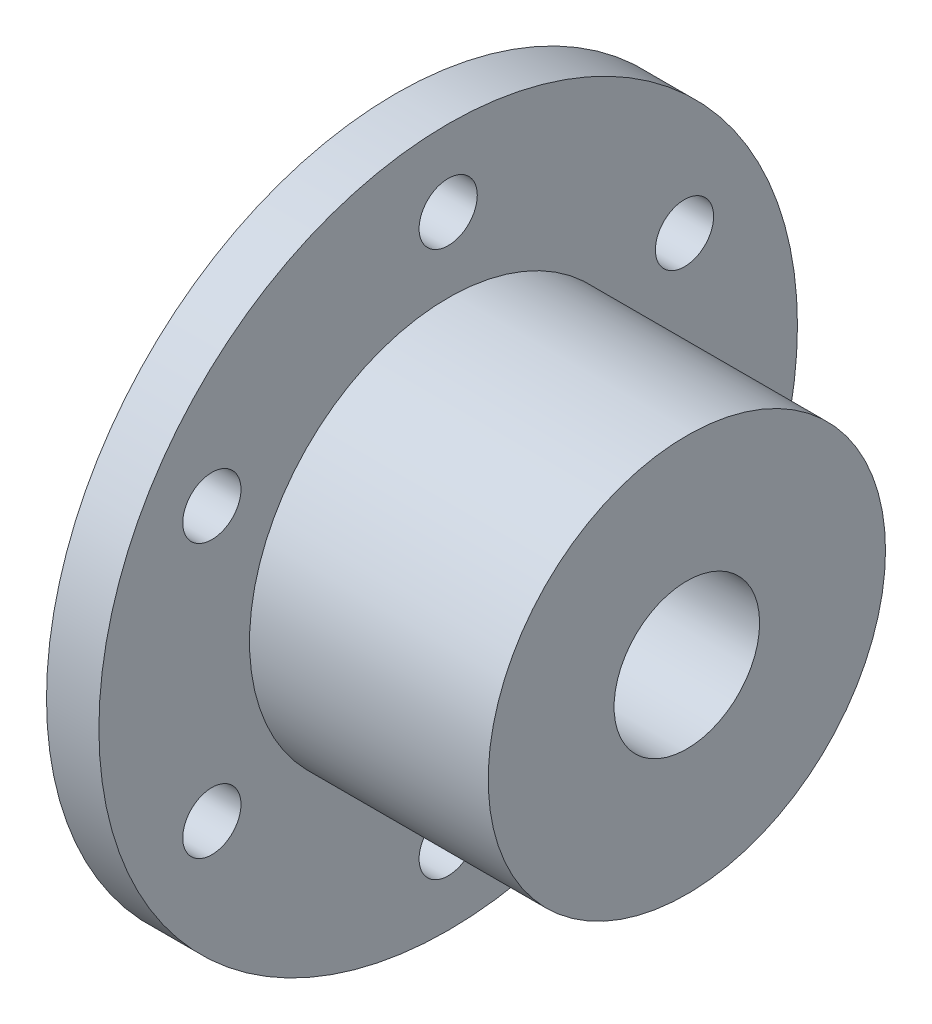
SolidWorks part; units mm, degrees
ref_plane "Front Plane" through (0, 0, 0) normal (0, 0, 1) x (1, 0, 0)
ref_plane "Top Plane" through (0, 0, 0) normal (0, 1, 0) x (1, 0, 0)
ref_plane "Right Plane" through (0, 0, 0) normal (1, 0, 0) x (0, 0, -1)
sketch "Sketch1" plane through (0, 0, 0) normal (1, 0, 0) x (0, 0, -1)
  circle A0 centre (0, 0) radius 30.48
  circle A1 centre (0, 0) radius 6.35
  circle A2 centre (0, 0) radius 23.8125 construction
  circle A3 centre (0, 23.8125) radius 2.54
  circle A4 centre (20.6222, 11.9063) radius 2.54
  circle A5 centre (20.6222, -11.9062) radius 2.54
  circle A6 centre (0, -23.8125) radius 2.54
  circle A7 centre (-20.6222, -11.9063) radius 2.54
  circle A8 centre (-20.6222, 11.9062) radius 2.54
  point P20 (0, 0)
  dimension "D1" = 6
extrude "Boss-Extrude1" add sketch "Sketch1" along normal mid plane 25.4
sketch "Sketch2" plane through (12.7, 0, 0) normal (1, 0, 0) x (0, 0, -1)
  circle A0 centre (0, 0) radius 17.3355
extrude "Cut-Extrude1" cut sketch "Sketch2" against normal blind 20.828 flip side to cut
ref_plane "Flange centre" through (-10.414, 0, 0) normal (-1, 0, 0) x (0, 0, 1)
